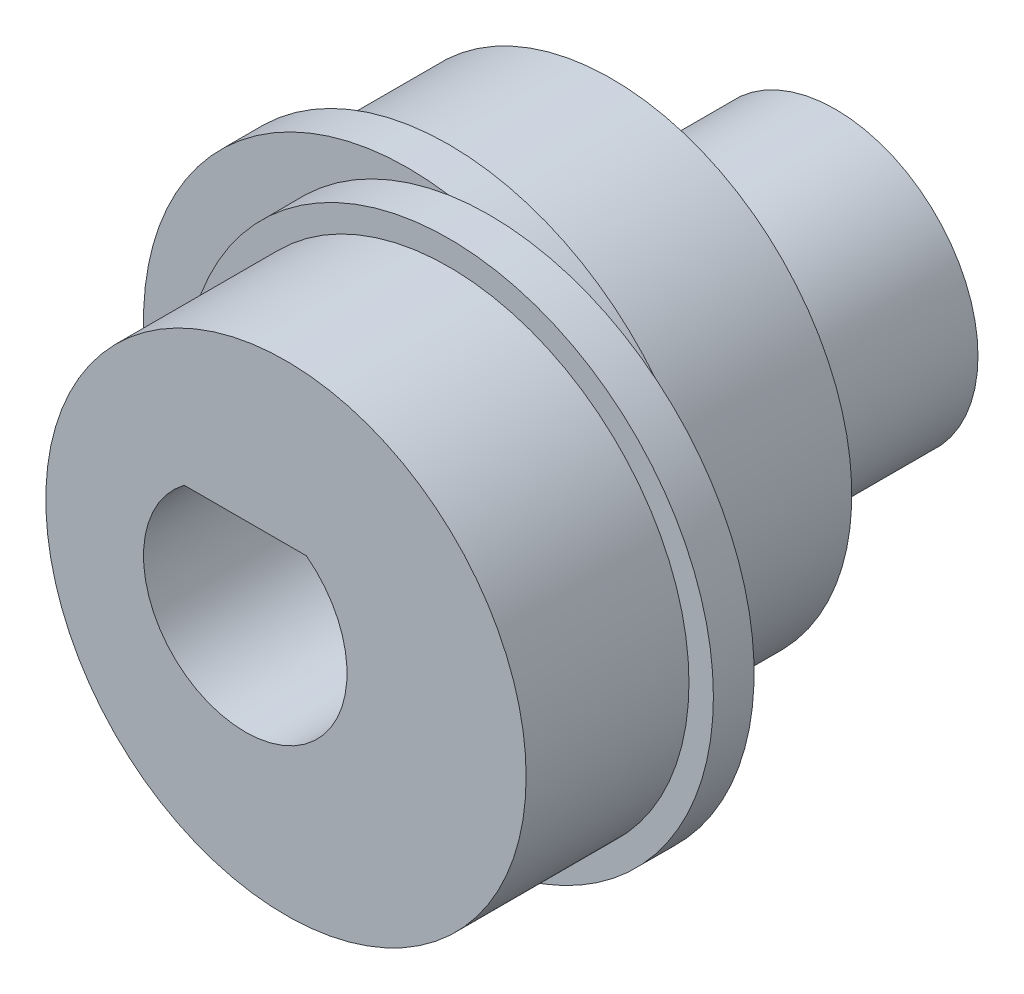
SolidWorks part; units mm, degrees
ref_plane "Front Plane" through (0, 0, 0) normal (0, 0, 1) x (1, 0, 0)
ref_plane "Top Plane" through (0, 0, 0) normal (0, 1, 0) x (1, 0, 0)
ref_plane "Right Plane" through (0, 0, 0) normal (1, 0, 0) x (0, 0, -1)
sketch "Sketch1" plane through (0, 0, 0) normal (0, 0, 1) x (1, 0, 0)
  line L0 (0, -2.5) -> (0, 2) construction
  line L1 (-1.5, 2) -> (1.5, 2)
  arc A0 (-1.5, 2) -> (1.5, 2) centre (0, 0) ccw
  circle A1 centre (0, 0) radius 3.5
  dimension "D1" = 4.5
  dimension "D2" = 7
  dimension "2.6" = 2.5
extrude "Boss-Extrude1" add sketch "Sketch1" along normal blind 10
sketch "Sketch2" plane through (0, 0, 0) normal (0, 0, -1) x (-1, 0, 0)
  line L0 (0, 0) -> (1, 0) construction
  circle A3 centre (1, 0) radius 5.9
  circle A5 centre (0, 0) radius 3.5 construction
  circle A6 centre (0, 0) radius 3.5
  dimension "D2" = 11.8
  dimension "D1" = 1
extrude "Boss-Extrude2" add sketch "Sketch2" against normal blind 4
sketch "Sketch3" plane through (0, 0, 4) normal (0, 0, 1) x (1, 0, 0)
  line L0 (1.5, 2) -> (-1.5, 2) construction
  line L1 (1.5, 2) -> (-1.5, 2)
  circle A2 centre (-1, 0) radius 6.5
  arc A3 (-1.5, 2) -> (1.5, 2) centre (0, 0) ccw construction
  arc A4 (-1.5, 2) -> (1.5, 2) centre (0, 0) ccw
  dimension "D1" = 13
extrude "Boss-Extrude3" add sketch "Sketch3" along normal blind 1
sketch "Sketch4" plane through (0, 0, 5) normal (0, 0, 1) x (1, 0, 0)
  line L0 (0, 0) -> (1, 0) construction
  line L1 (1.5, 2) -> (-1.5, 2) construction
  line L2 (1.5, 2) -> (-1.5, 2)
  circle A0 centre (1, 0) radius 6.5
  arc A1 (-1.5, 2) -> (1.5, 2) centre (0, 0) ccw construction
  arc A2 (-1.5, 2) -> (1.5, 2) centre (0, 0) ccw
  dimension "D2" = 13
  dimension "D1" = 1
extrude "Boss-Extrude4" add sketch "Sketch4" along normal blind 1
sketch "Sketch5" plane through (0, 0, 6) normal (0, 0, 1) x (1, 0, 0)
  line L0 (0, 0) -> (1, 0) construction
  line L1 (1.5, 2) -> (-1.5, 2) construction
  line L2 (1.5, 2) -> (-1.5, 2)
  circle A0 centre (1, 0) radius 5.9
  arc A1 (-1.5, 2) -> (1.5, 2) centre (0, 0) ccw construction
  arc A2 (-1.5, 2) -> (1.5, 2) centre (0, 0) ccw
  dimension "D2" = 11.8
  dimension "D1" = 1
extrude "Boss-Extrude5" add sketch "Sketch5" along normal blind 4
extrude "Boss-Extrude6" add sketch "Sketch1<2>" against normal blind 4.5
sketch "Sketch1<2>" plane through (0, 0, 0) normal (0, 0, 1) x (1, 0, 0) same geometry as "Sketch1"
